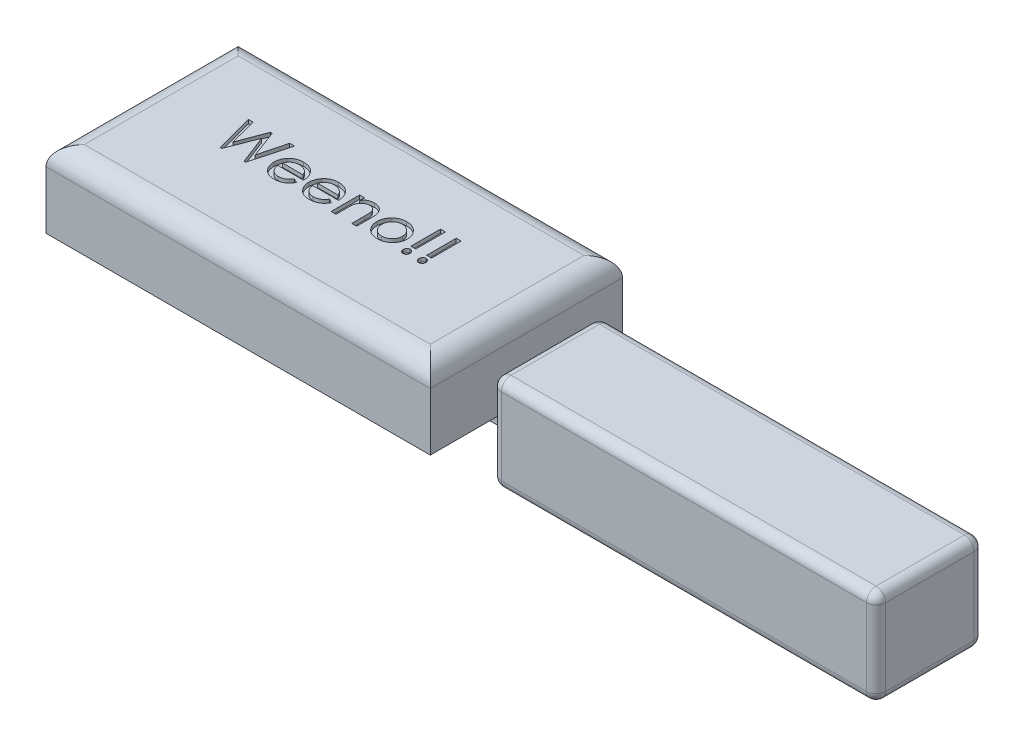
SolidWorks part; units mm, degrees
ref_plane "Front Plane" through (0, 0, 0) normal (0, 0, 1) x (1, 0, 0)
ref_plane "Top Plane" through (0, 0, 0) normal (0, 1, 0) x (1, 0, 0)
ref_plane "Right Plane" through (0, 0, 0) normal (1, 0, 0) x (0, 0, -1)
sketch "Sketch1" plane through (0, 0, 0) normal (0, 1, 0) x (1, 0, 0)
  line L1 (-50, 25) -> (50, 25)
  line L2 (-50, 25) -> (-50, -25)
  line L3 (-50, -25) -> (50, -25)
  line L4 (50, 25) -> (50, -25)
  line L5 (50, 6) -> (55, 6)
  line L6 (50, 6) -> (50, -6)
  line L7 (50, -6) -> (55, -6)
  line L8 (55, 6) -> (55, -6)
  line L9 (55, 14) -> (155, 14)
  line L10 (55, 14) -> (55, -14)
  line L11 (55, -14) -> (155, -14)
  line L12 (155, 14) -> (155, -14)
  point P8 (-50, 0)
  point P10 (0, 25)
  point P11 (55, 0)
  point P16 (155, 0)
  dimension "D1" = 100
  dimension "D2" = 50
  dimension "D3" = 5
  dimension "D4" = 12
  dimension "D5" = 100
  dimension "D6" = 28
extrude "Boss-Extrude1" add sketch "Sketch1" along normal blind 20 contours L4 L1 L2 L3 region at (0, 0, 0)
extrude "Boss-Extrude2" add sketch "Sketch1<3>" along normal blind 1 and the other way blind 3.5 contours L8 L5 L4 L7 region at (52.5, 0, 0)
sketch "Sketch1<3>" plane through (0, 0, 0) normal (0, 1, 0) x (1, 0, 0) same geometry as "Sketch1"
extrude "Boss-Extrude3" add sketch "Sketch1<4>" along normal blind 15 and the other way blind 10 contours L12 L9 L10 L8 L11 region at (105, 0, 0)
sketch "Sketch1<4>" plane through (0, 0, 0) normal (0, 1, 0) x (1, 0, 0) same geometry as "Sketch1"
sketch "Sketch2" plane through (50, 0, 0) normal (-1, 0, 0) x (0, 0, 1)
  line L4 (6, 0) -> (-6, 0)
  line L5 (-6, 0) -> (-6, -3.5)
  line L6 (-6, -3.5) -> (6, -3.5)
  line L7 (6, -3.5) -> (6, 0)
  line L8 (6, 0) -> (-6, 0)
  line L9 (-6, 0) -> (-6, -3.5)
  line L10 (-6, -3.5) -> (6, -3.5)
  line L11 (6, -3.5) -> (6, 0)
  dimension "D1" = 0
extrude "Boss-Extrude4" add sketch "Sketch2" along normal blind 4.5
fillet "Fillet1" radius 2.5 12 edges at (55, 2.5, -14) (105, -10, -14) (55, -10, 0) (105, -10, 14) (55, 2.5, 14) (105, 15, 14) (55, 15, 0) (105, 15, -14) (155, -10, 0) (155, 2.5, 14) (155, 15, 0) (155, 2.5, -14)
sketch "Sketch3" plane through (0, 20, 0) normal (0, 1, 0) x (1, 0, 0)
  line L0 (-50, 25) -> (-50, -25) construction
  line L1 (-50, -25) -> (50, -25) construction
  text T0 "<b>Weeno!!</b>" font "Century Gothic" height 10
  point P1 (-20.7792, -4.3367)
  point P2 (-30.5631, -1.8979)
  point P3 (-31.2422, 2.5647)
  point P4 (-31.1451, -2.383)
  point P5 (0, 0)
  point P6 (0, 0)
  point P7 (0, 0)
  point P8 (-26.8765, -2.1889)
  dimension "D1" = 20
  dimension "D2" = 22
extrude "Cut-Extrude1" cut sketch "Sketch3" against normal blind 1
fillet "Fillet2" radius 5 4 edges at (0, 20, 25) (50, 20, 0) (0, 20, -25) (-50, 20, 0)
